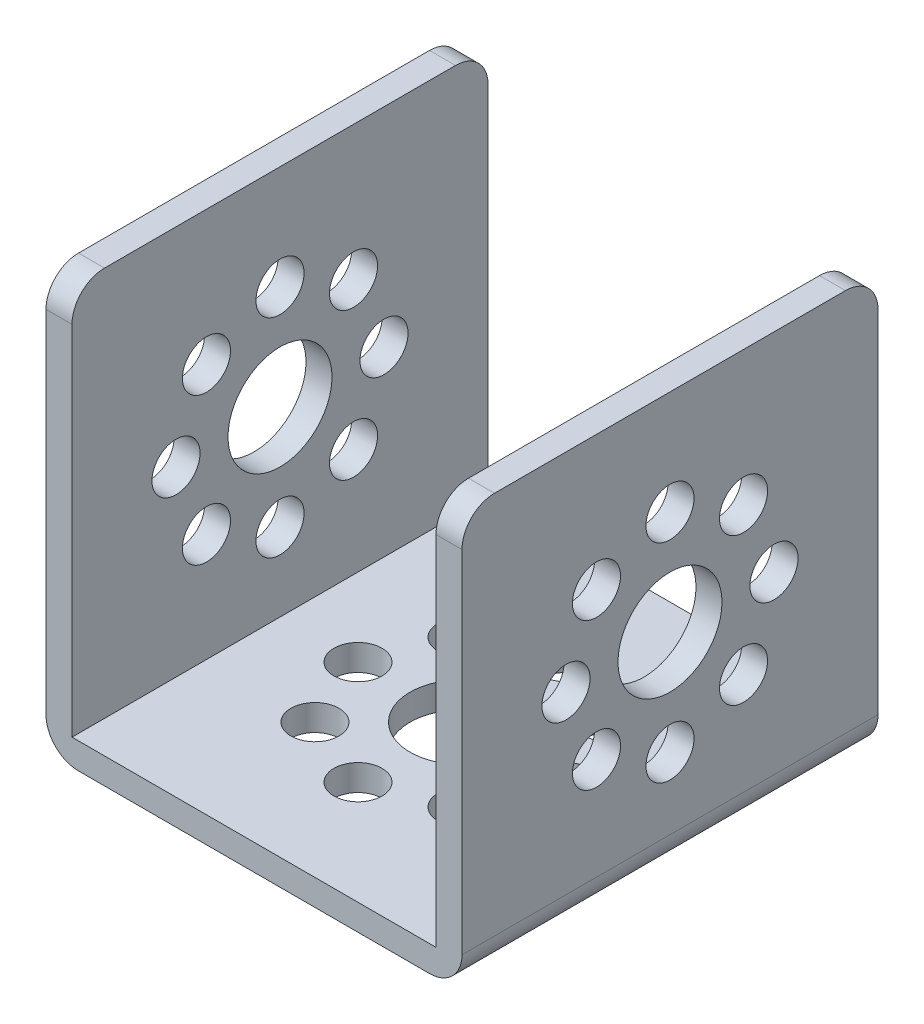
SolidWorks part; units mm, degrees
material "2024 Alloy"
ref_plane "Front Plane" through (0, 0, 0) normal (0, 0, 1) x (1, 0, 0)
ref_plane "Top Plane" through (0, 0, 0) normal (0, 1, 0) x (1, 0, 0)
ref_plane "Right Plane" through (0, 0, 0) normal (1, 0, 0) x (0, 0, -1)
ref_plane "Plane1" through (16, 0, 0) normal (1, 0, 0) x (0, 0, -1)
sketch "Sketch1" plane through (16, 0, 0) normal (1, 0, 0) x (0, 0, -1)
  line L0 (-16, 32) -> (-16, 0)
  line L1 (-16, 0) -> (16, 0)
  line L2 (16, 0) -> (16, 32)
  line L3 (16, 32) -> (-16, 32)
extrude "Boss-Extrude1" add sketch "Sketch1" against normal blind 32
sketch "Sketch2" plane through (0, 0, -16) normal (0, 0, -1) x (-1, 0, 0)
  line L0 (14, 32) -> (-14, 32)
  line L1 (-14, 32) -> (-14, 2)
  line L2 (-14, 2) -> (14, 2)
  line L3 (14, 2) -> (14, 32)
extrude "Cut-Extrude1" cut sketch "Sketch2" against normal through all
hole_wizard "Ø8.0 (8) Diameter Hole1" positions "Sketch4" profile "Sketch3" hole size "Ø8.0" standard "ANSI Metric"
sketch "Sketch4" plane through (-16, 0, 0) normal (-1, 0, 0) x (0, 0, 1)
  point P0 (0, 16)
sketch "Sketch3" plane through (-16, 16, 0) normal (0, 1, 0) x (0, 0, 1)
  line L0 (0, 0) -> (0, 2)
  line L1 (0, 2) -> (4, 2)
  line L2 (4, 2) -> (4, 0)
  line L5 (4, 0) -> (0, 0)
  line L11 (0, -6.35) -> (0, 107.95) construction
  dimension "Thru Hole Dia." = 8
  dimension "Thru Hole Depth" = 2
hole_wizard "Ø3.7 (3.7) Diameter Hole1" positions "Sketch6" profile "Sketch5" hole size "Ø3.7" standard "ANSI Metric"
sketch "Sketch6" plane through (-16, 0, 0) normal (-1, 0, 0) x (0, 0, 1)
  point P0 (-8, 16)
  point P1 (0, 24)
  point P2 (8, 16)
  point P3 (0, 8)
  point P4 (-5.6569, 21.6569)
  point P5 (5.6569, 21.6569)
  point P6 (5.6569, 10.3431)
  point P7 (-5.6569, 10.3431)
sketch "Sketch5" plane through (-16, 16, -8) normal (0, 1, 0) x (0, 0, 1)
  line L0 (0, 0) -> (0, 2)
  line L1 (0, 2) -> (1.85, 2)
  line L2 (1.85, 2) -> (1.85, 0)
  line L5 (1.85, 0) -> (0, 0)
  line L11 (0, -6.35) -> (0, 107.95) construction
  dimension "Thru Hole Dia." = 3.7
  dimension "Thru Hole Depth" = 2
hole_wizard "Ø3.7 (3.7) Diameter Hole2" positions "Sketch8" profile "Sketch7" hole size "Ø3.7" standard "ANSI Metric"
sketch "Sketch8" plane through (0, 2, 0) normal (0, 1, 0) x (1, 0, 0)
  point P0 (8, 0)
  point P1 (0, 8)
  point P2 (-8, 0)
  point P3 (0, -8)
  point P4 (5.6569, 5.6569)
  point P5 (-5.6569, 5.6569)
  point P6 (-5.6569, -5.6569)
  point P7 (5.6569, -5.6569)
sketch "Sketch7" plane through (8, 2, 0) normal (1, 0, 0) x (0, 0, 1)
  line L0 (0, 0) -> (0, 2)
  line L1 (0, 2) -> (1.85, 2)
  line L2 (1.85, 2) -> (1.85, 0)
  line L5 (1.85, 0) -> (0, 0)
  line L11 (0, -6.35) -> (0, 107.95) construction
  dimension "Thru Hole Dia." = 3.7
  dimension "Thru Hole Depth" = 2
hole_wizard "Ø8.0 (8) Diameter Hole2" positions "Sketch10" profile "Sketch9" hole size "Ø8.0" standard "ANSI Metric"
sketch "Sketch10" plane through (0, 0, 0) normal (0, -1, 0) x (-1, 0, 0)
  point P0 (0, 0)
sketch "Sketch9" plane through (0, 0, 0) normal (1, 0, 0) x (0, 0, -1)
  line L0 (0, 0) -> (0, 32)
  line L1 (0, 32) -> (4, 32)
  line L2 (4, 32) -> (4, 0)
  line L5 (4, 0) -> (0, 0)
  line L11 (0, -6.35) -> (0, 107.95) construction
  dimension "Thru Hole Dia." = 8
  dimension "Thru Hole Depth" = 32
hole_wizard "Ø8.0 (8) Diameter Hole3" positions "Sketch12" profile "Sketch11" hole size "Ø8.0" standard "ANSI Metric"
sketch "Sketch12" plane through (16, 0, 0) normal (1, 0, 0) x (0, 0, -1)
  point P0 (0, 16)
sketch "Sketch11" plane through (16, 16, 0) normal (0, 1, 0) x (0, 0, -1)
  line L0 (0, 0) -> (0, 32)
  line L1 (0, 32) -> (4, 32)
  line L2 (4, 32) -> (4, 0)
  line L5 (4, 0) -> (0, 0)
  line L11 (0, -6.35) -> (0, 107.95) construction
  dimension "Thru Hole Dia." = 8
  dimension "Thru Hole Depth" = 32
hole_wizard "Ø3.7 (3.7) Diameter Hole3" positions "Sketch14" profile "Sketch13" hole size "Ø3.7" standard "ANSI Metric"
sketch "Sketch14" plane through (16, 0, 0) normal (1, 0, 0) x (0, 0, -1)
  point P0 (8, 16)
  point P1 (0, 24)
  point P2 (-8, 16)
  point P3 (0, 8)
  point P4 (5.6569, 21.6569)
  point P5 (-5.6569, 21.6569)
  point P6 (-5.6569, 10.3431)
  point P7 (5.6569, 10.3431)
sketch "Sketch13" plane through (16, 16, -8) normal (0, 1, 0) x (0, 0, -1)
  line L0 (0, 0) -> (0, 32)
  line L1 (0, 32) -> (1.85, 32)
  line L2 (1.85, 32) -> (1.85, 0)
  line L5 (1.85, 0) -> (0, 0)
  line L11 (0, -6.35) -> (0, 107.95) construction
  dimension "Thru Hole Dia." = 3.7
  dimension "Thru Hole Depth" = 32
fillet "Fillet1" radius 2.5 6 edges at (-16, 0, 0) (-15, 32, 16) (-15, 32, -16) (16, 0, 0) (15, 32, 16) (15, 32, -16) tangent propagation no
